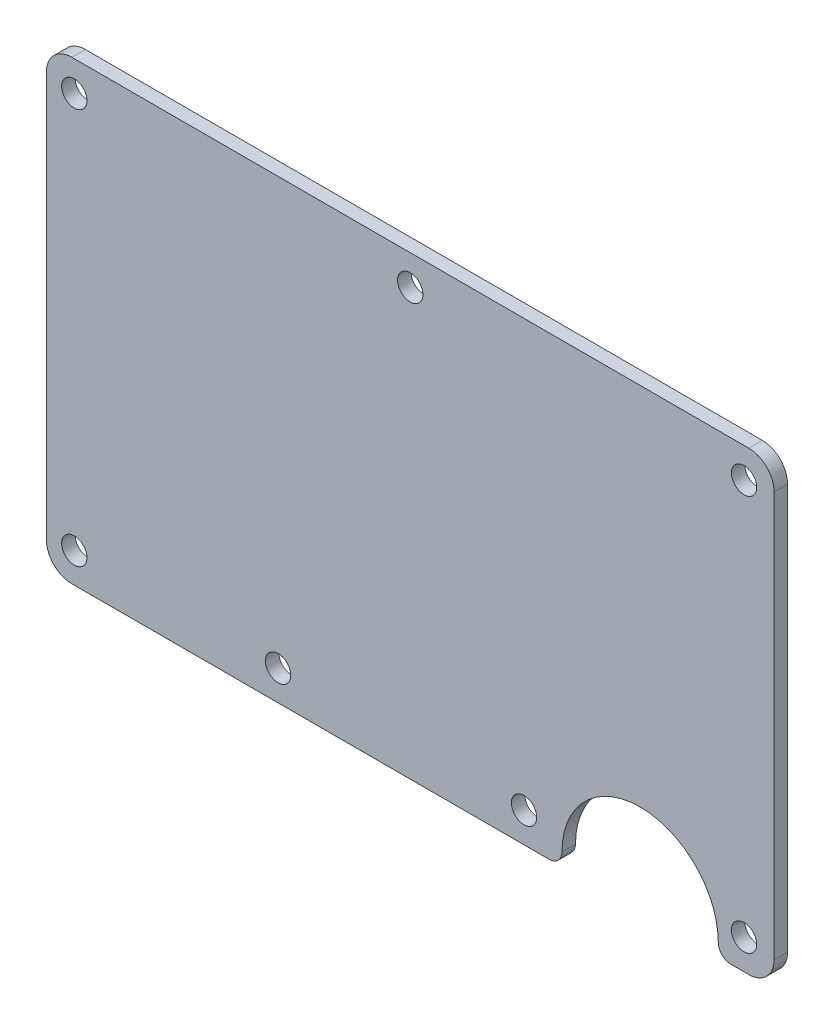
SolidWorks part; units mm, degrees
ref_plane "Front Plane" through (0, 0, 0) normal (0, 0, 1) x (1, 0, 0)
ref_plane "Top Plane" through (0, 0, 0) normal (0, 1, 0) x (1, 0, 0)
ref_plane "Right Plane" through (0, 0, 0) normal (1, 0, 0) x (0, 0, -1)
ref_plane "Plane1" through (0, 0, 1.6) normal (0, 0, 1) x (1, 0, 0)
sketch "Sketch1" plane through (0, 0, 1.6) normal (0, 0, 1) x (1, 0, 0)
  line L0 (0, 50.9476) -> (0, 3)
  line L1 (3, 0) -> (59.5, 0)
  line L2 (81, 0) -> (83.1, 0)
  line L3 (86.1, 3) -> (86.1, 50.9476)
  line L4 (83.1, 53.9476) -> (3, 53.9476)
  circle A0 centre (3.302, 50.3904) radius 1.5
  circle A1 centre (3.302, 3.556) radius 1.5
  circle A2 centre (82.55, 3.556) radius 1.5
  circle A3 centre (82.55, 50.3904) radius 1.5
  circle A4 centre (27.4096, 3.556) radius 1.5
  circle A5 centre (56.515, 3.556) radius 1.5
  circle A6 centre (43.05, 50.3904) radius 1.5
  arc A7 (0, 3) -> (3, 0) centre (3, 3) ccw
  arc A8 (59.5, 0) -> (61, 1.5) centre (59.5, 1.5) ccw
  arc A9 (61, 1.5) -> (79.5, 1.5) centre (70.25, 1.5) cw
  arc A10 (79.5, 1.5) -> (81, 0) centre (81, 1.5) ccw
  arc A11 (83.1, 0) -> (86.1, 3) centre (83.1, 3) ccw
  arc A12 (86.1, 50.9476) -> (83.1, 53.9476) centre (83.1, 50.9476) ccw
  arc A13 (3, 53.9476) -> (0, 50.9476) centre (3, 50.9476) ccw
extrude "Boss-Extrude1" add sketch "Sketch1" against normal blind 1.6
